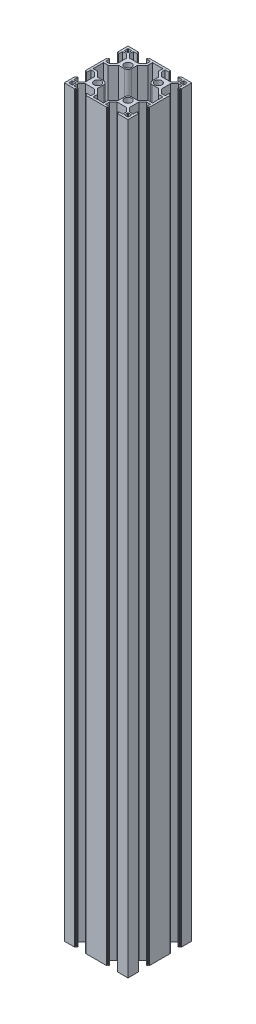
SolidWorks part; units mm, degrees
ref_plane "Front Plane" through (0, 0, 0) normal (0, 0, 1) x (1, 0, 0)
ref_plane "Top Plane" through (0, 0, 0) normal (0, 1, 0) x (1, 0, 0)
ref_plane "Right Plane" through (0, 0, 0) normal (1, 0, 0) x (0, 0, -1)
sketch "Sketch1" plane through (0, 0, 0) normal (0, 1, 0) x (1, 0, 0)
  line L0 (0, 30) -> (0, -30) construction
  line L1 (-30, -30) -> (30, -30)
  line L2 (-30, -30) -> (-30, 30)
  line L3 (-30, 30) -> (30, 30)
  line L4 (30, -30) -> (30, 30)
  line L5 (-30, -30) -> (30, 30) construction
  line L6 (-30, 30) -> (30, -30) construction
  line L7 (-30, 0) -> (30, 0) construction
  line L8 (-23.05, -28) -> (-6.95, -28)
  line L9 (-6.95, -28) -> (-6.95, -24.4)
  line L10 (-6.95, -24.4) -> (-10.615, -20.8)
  line L11 (-10.615, -20.8) -> (-19.385, -20.8)
  line L12 (-19.385, -20.8) -> (-23.05, -24.4)
  line L13 (-23.05, -24.4) -> (-23.05, -28)
  line L14 (10.615, -20.8) -> (19.385, -20.8)
  line L15 (6.95, -24.4) -> (10.615, -20.8)
  line L16 (6.95, -28) -> (6.95, -24.4)
  line L17 (23.05, -28) -> (6.95, -28)
  line L18 (23.05, -24.4) -> (23.05, -28)
  line L19 (19.385, -20.8) -> (23.05, -24.4)
  line L20 (19.385, 20.8) -> (23.05, 24.4)
  line L21 (23.05, 24.4) -> (23.05, 28)
  line L22 (23.05, 28) -> (6.95, 28)
  line L23 (6.95, 28) -> (6.95, 24.4)
  line L24 (6.95, 24.4) -> (10.615, 20.8)
  line L25 (10.615, 20.8) -> (19.385, 20.8)
  line L26 (-23.05, 24.4) -> (-23.05, 28)
  line L27 (-19.385, 20.8) -> (-23.05, 24.4)
  line L28 (-10.615, 20.8) -> (-19.385, 20.8)
  line L29 (-6.95, 24.4) -> (-10.615, 20.8)
  line L30 (-6.95, 28) -> (-6.95, 24.4)
  line L31 (-23.05, 28) -> (-6.95, 28)
  line L32 (-20.8, 19.385) -> (-24.4, 23.05)
  line L33 (-24.4, 23.05) -> (-28, 23.05)
  line L34 (-28, 23.05) -> (-28, 6.95)
  line L35 (-28, 6.95) -> (-24.4, 6.95)
  line L36 (-24.4, 6.95) -> (-20.8, 10.615)
  line L37 (-20.8, 10.615) -> (-20.8, 19.385)
  line L38 (-24.4, -23.05) -> (-28, -23.05)
  line L39 (-20.8, -19.385) -> (-24.4, -23.05)
  line L40 (-20.8, -10.615) -> (-20.8, -19.385)
  line L41 (-24.4, -6.95) -> (-20.8, -10.615)
  line L42 (-28, -6.95) -> (-24.4, -6.95)
  line L43 (-28, -23.05) -> (-28, -6.95)
  line L44 (20.8, -19.385) -> (24.4, -23.05)
  line L45 (24.4, -23.05) -> (28, -23.05)
  line L46 (28, -23.05) -> (28, -6.95)
  line L47 (28, -6.95) -> (24.4, -6.95)
  line L48 (24.4, -6.95) -> (20.8, -10.615)
  line L49 (20.8, -10.615) -> (20.8, -19.385)
  line L50 (24.4, 23.05) -> (28, 23.05)
  line L51 (20.8, 19.385) -> (24.4, 23.05)
  line L52 (20.8, 10.615) -> (20.8, 19.385)
  line L53 (24.4, 6.95) -> (20.8, 10.615)
  line L54 (28, 6.95) -> (24.4, 6.95)
  line L55 (28, 23.05) -> (28, 6.95)
  point P0 (0, 0)
  dimension "D1" = 60
  dimension "D2" = 16.1
  dimension "D3" = 8.77
  dimension "D4" = 3.6
  dimension "D5" = 7.2
  dimension "D6" = 2
  dimension "D7" = 6.95
extrude "Boss-Extrude1" add sketch "Sketch1" along normal blind 700
sketch "Sketch2" plane through (0, 700, 0) normal (0, 1, 0) x (1, 0, 0)
  line L0 (-19.1, -28) -> (-19.1, -29)
  line L1 (-23.05, -28) -> (-6.95, -28) construction
  line L2 (-30, -30) -> (30, -30) construction
  line L3 (-10.9, -28) -> (-10.9, -29)
  line L4 (-10.9, -29) -> (-9.9, -29)
  line L5 (-9.9, -29) -> (-9.9, -30)
  line L6 (-19.1, -29) -> (-20.1, -29)
  line L7 (-20.1, -29) -> (-20.1, -30)
  line L8 (-19.1, -28) -> (-10.9, -28)
  line L9 (-20.1, -30) -> (-9.9, -30)
  dimension "D1" = 8.2
  dimension "D2" = 3.95
  dimension "D3" = 1
  dimension "D4" = 1
extrude "Cut-Extrude1" cut sketch "Sketch2" against normal through all
mirror "Mirror1" about plane through (0, 0, 0) normal (1, 0, 0) of "Cut-Extrude1"
ref_axis "Axis1" through (0, 1050, 0) along (0, -1, 0)
pattern_circular "CirPattern1" count 4 over 360 about axis through (0, 1050, 0) along (0, -1, 0) of "Cut-Extrude1", "Mirror1"
sketch "Sketch4" plane through (0, 700, 0) normal (0, 1, 0) x (1, 0, 0)
  line L0 (19.385, 18.8) -> (9.797, 18.8) construction
  line L1 (-18.8, 18.8) -> (-18.8, 9.797)
  line L2 (18.8, -19.385) -> (18.8, -9.797) construction
  line L3 (28, 4.95) -> (28, -4.95)
  line L4 (-18.8, -9.797) -> (-18.8, -19.385) construction
  line L5 (4.95, -28) -> (-4.95, -28)
  line L6 (-9.797, 18.8) -> (-9.797, 13.197)
  line L7 (-28, -4.95) -> (-28, 4.95)
  line L8 (-18.8, 9.797) -> (-23.5611, 4.95)
  line L9 (-23.5611, 4.95) -> (-28, 4.95)
  line L10 (18.8, 18.8) -> (9.797, 18.8)
  line L11 (9.797, 18.8) -> (4.95, 23.5611)
  line L12 (4.95, 23.5611) -> (4.95, 28)
  line L13 (4.95, 28) -> (4.95, 28)
  line L14 (4.95, 28) -> (4.95, 28)
  line L15 (4.95, 28) -> (4.95, 28)
  line L16 (4.95, 28) -> (4.95, 28)
  line L17 (4.95, 28) -> (-4.95, 28)
  line L18 (-4.95, 28) -> (-4.95, 28)
  line L19 (-4.95, 28) -> (-4.95, 28)
  line L20 (-4.95, 28) -> (-4.95, 28)
  line L21 (-4.95, 28) -> (-4.95, 28)
  line L22 (-4.95, 28) -> (-4.95, 23.5611)
  line L23 (-4.95, 23.5611) -> (-9.797, 18.8)
  line L24 (-9.797, 18.8) -> (-18.8, 18.8)
  line L25 (28, 4.95) -> (23.5611, 4.95)
  line L26 (23.5611, 4.95) -> (18.8, 9.797)
  line L27 (18.8, 9.797) -> (18.8, 18.8)
  line L28 (18.8, -18.8) -> (18.8, -9.797)
  line L29 (18.8, -9.797) -> (23.5611, -4.95)
  line L30 (23.5611, -4.95) -> (28, -4.95)
  line L31 (4.95, -28) -> (4.95, -23.5611)
  line L32 (4.95, -23.5611) -> (9.797, -18.8)
  line L33 (9.797, -18.8) -> (18.8, -18.8)
  line L34 (-18.8, -18.8) -> (-9.797, -18.8)
  line L35 (-9.797, -18.8) -> (-4.95, -23.5611)
  line L36 (-4.95, -23.5611) -> (-4.95, -28)
  line L37 (-28, -4.95) -> (-23.5611, -4.95)
  line L38 (-23.5611, -4.95) -> (-18.8, -9.797)
  line L39 (-18.8, -9.797) -> (-18.8, -18.8)
  line L40 (-9.797, 18.8) -> (-19.385, 18.8) construction
  line L41 (-18.8, 19.385) -> (-18.8, 9.797) construction
  line L42 (18.8, 9.797) -> (18.8, 19.385) construction
  line L43 (9.797, -18.8) -> (19.385, -18.8) construction
  line L44 (-19.385, -18.8) -> (-9.797, -18.8) construction
  line L45 (-13.197, 9.797) -> (-18.8, 9.797)
  line L46 (9.797, 18.8) -> (9.797, 13.197)
  line L47 (13.197, 9.797) -> (18.8, 9.797)
  line L48 (-18.8, -9.797) -> (-13.197, -9.797)
  line L49 (-9.797, -13.197) -> (-9.797, -18.8)
  line L50 (9.797, -18.8) -> (9.797, -13.197)
  line L51 (13.197, -9.797) -> (18.8, -9.797)
  line L52 (-27.5, -28) -> (-24.9, -28)
  line L53 (24.9, -28) -> (27.5, -28)
  line L54 (24.4, -27.5) -> (24.4, -24.9)
  line L55 (24.9, -24.4) -> (27.5, -24.4)
  line L56 (28, -27.5) -> (28, -24.9)
  line L57 (24.4, -28) -> (28, -24.4) construction
  line L58 (24.4, -24.4) -> (28, -28) construction
  line L59 (-28, -24.9) -> (-28, -27.5)
  line L60 (-27.5, -24.4) -> (-24.9, -24.4)
  line L61 (-24.4, -24.9) -> (-24.4, -27.5)
  line L62 (-28, 27.5) -> (-28, 24.9)
  line L63 (-24.9, 28) -> (-27.5, 28)
  line L64 (-24.4, 27.5) -> (-24.4, 24.9)
  line L65 (-24.9, 24.4) -> (-27.5, 24.4)
  line L66 (27.5, 28) -> (24.9, 28)
  line L67 (28, 24.9) -> (28, 27.5)
  line L68 (27.5, 24.4) -> (24.9, 24.4)
  line L69 (24.4, 24.9) -> (24.4, 27.5)
  line L116 (28, 19.1) -> (29, 19.1)
  line L117 (29, 19.1) -> (29, 20.1)
  line L118 (29, 20.1) -> (30, 20.1)
  line L119 (30, 20.1) -> (30, 30)
  line L120 (30, 30) -> (20.1, 30)
  line L121 (20.1, 30) -> (20.1, 29)
  line L122 (20.1, 29) -> (19.1, 29)
  line L123 (19.1, 29) -> (19.1, 28)
  line L124 (19.1, 28) -> (23.05, 28)
  line L125 (23.05, 28) -> (23.05, 24.4)
  line L126 (23.05, 24.4) -> (19.385, 20.8)
  line L127 (19.385, 20.8) -> (10.615, 20.8)
  line L128 (10.615, 20.8) -> (6.95, 24.4)
  line L129 (6.95, 24.4) -> (6.95, 28)
  line L130 (6.95, 28) -> (10.9, 28)
  line L131 (10.9, 28) -> (10.9, 29)
  line L132 (10.9, 29) -> (9.9, 29)
  line L133 (9.9, 29) -> (9.9, 30)
  line L134 (9.9, 30) -> (-9.9, 30)
  line L135 (-9.9, 30) -> (-9.9, 29)
  line L136 (-9.9, 29) -> (-10.9, 29)
  line L137 (-10.9, 29) -> (-10.9, 28)
  line L138 (-10.9, 28) -> (-6.95, 28)
  line L139 (-6.95, 28) -> (-6.95, 24.4)
  line L140 (-6.95, 24.4) -> (-10.615, 20.8)
  line L141 (-10.615, 20.8) -> (-19.385, 20.8)
  line L142 (-19.385, 20.8) -> (-23.05, 24.4)
  line L143 (-23.05, 24.4) -> (-23.05, 28)
  line L144 (-23.05, 28) -> (-19.1, 28)
  line L145 (-19.1, 28) -> (-19.1, 29)
  line L146 (-19.1, 29) -> (-20.1, 29)
  line L147 (-20.1, 29) -> (-20.1, 30)
  line L148 (-20.1, 30) -> (-30, 30)
  line L149 (-30, 30) -> (-30, 20.1)
  line L150 (-30, 20.1) -> (-29, 20.1)
  line L151 (-29, 20.1) -> (-29, 19.1)
  line L152 (-29, 19.1) -> (-28, 19.1)
  line L153 (-28, 19.1) -> (-28, 23.05)
  line L154 (-28, 23.05) -> (-24.4, 23.05)
  line L155 (-24.4, 23.05) -> (-20.8, 19.385)
  line L156 (-20.8, 19.385) -> (-20.8, 10.615)
  line L157 (-20.8, 10.615) -> (-24.4, 6.95)
  line L158 (-24.4, 6.95) -> (-28, 6.95)
  line L159 (-28, 6.95) -> (-28, 10.9)
  line L160 (-28, 10.9) -> (-29, 10.9)
  line L161 (-29, 10.9) -> (-29, 9.9)
  line L162 (-29, 9.9) -> (-30, 9.9)
  line L163 (-30, 9.9) -> (-30, -9.9)
  line L164 (-30, -9.9) -> (-29, -9.9)
  line L165 (-29, -9.9) -> (-29, -10.9)
  line L166 (-29, -10.9) -> (-28, -10.9)
  line L167 (-28, -10.9) -> (-28, -6.95)
  line L168 (-28, -6.95) -> (-24.4, -6.95)
  line L169 (-24.4, -6.95) -> (-20.8, -10.615)
  line L170 (-20.8, -10.615) -> (-20.8, -19.385)
  line L171 (-20.8, -19.385) -> (-24.4, -23.05)
  line L172 (-24.4, -23.05) -> (-28, -23.05)
  line L173 (-28, -23.05) -> (-28, -19.1)
  line L174 (-28, -19.1) -> (-29, -19.1)
  line L175 (-29, -19.1) -> (-29, -20.1)
  line L176 (-29, -20.1) -> (-30, -20.1)
  line L177 (-30, -20.1) -> (-30, -30)
  line L178 (-30, -30) -> (-20.1, -30)
  line L179 (-20.1, -30) -> (-20.1, -29)
  line L180 (-20.1, -29) -> (-19.1, -29)
  line L181 (-19.1, -29) -> (-19.1, -28)
  line L182 (-19.1, -28) -> (-23.05, -28)
  line L183 (-23.05, -28) -> (-23.05, -24.4)
  line L184 (-23.05, -24.4) -> (-19.385, -20.8)
  line L185 (-19.385, -20.8) -> (-10.615, -20.8)
  line L186 (-10.615, -20.8) -> (-6.95, -24.4)
  line L187 (-6.95, -24.4) -> (-6.95, -28)
  line L188 (-6.95, -28) -> (-10.9, -28)
  line L189 (-10.9, -28) -> (-10.9, -29)
  line L190 (-10.9, -29) -> (-9.9, -29)
  line L191 (-9.9, -29) -> (-9.9, -30)
  line L192 (-9.9, -30) -> (9.9, -30)
  line L193 (9.9, -30) -> (9.9, -29)
  line L194 (9.9, -29) -> (10.9, -29)
  line L195 (10.9, -29) -> (10.9, -28)
  line L196 (10.9, -28) -> (6.95, -28)
  line L197 (6.95, -28) -> (6.95, -24.4)
  line L198 (6.95, -24.4) -> (10.615, -20.8)
  line L199 (10.615, -20.8) -> (19.385, -20.8)
  line L200 (19.385, -20.8) -> (23.05, -24.4)
  line L201 (23.05, -24.4) -> (23.05, -28)
  line L202 (23.05, -28) -> (19.1, -28)
  line L203 (19.1, -28) -> (19.1, -29)
  line L204 (19.1, -29) -> (20.1, -29)
  line L205 (20.1, -29) -> (20.1, -30)
  line L206 (20.1, -30) -> (30, -30)
  line L207 (30, -30) -> (30, -20.1)
  line L208 (30, -20.1) -> (29, -20.1)
  line L209 (29, -20.1) -> (29, -19.1)
  line L210 (29, -19.1) -> (28, -19.1)
  line L211 (28, -19.1) -> (28, -23.05)
  line L212 (28, -23.05) -> (24.4, -23.05)
  line L213 (24.4, -23.05) -> (20.8, -19.385)
  line L214 (20.8, -19.385) -> (20.8, -10.615)
  line L215 (20.8, -10.615) -> (24.4, -6.95)
  line L216 (24.4, -6.95) -> (28, -6.95)
  line L217 (28, -6.95) -> (28, -10.9)
  line L218 (28, -10.9) -> (29, -10.9)
  line L219 (29, -10.9) -> (29, -9.9)
  line L220 (29, -9.9) -> (30, -9.9)
  line L221 (30, -9.9) -> (30, 9.9)
  line L222 (30, 9.9) -> (29, 9.9)
  line L223 (29, 9.9) -> (29, 10.9)
  line L224 (29, 10.9) -> (28, 10.9)
  line L225 (28, 10.9) -> (28, 6.95)
  line L226 (28, 6.95) -> (24.4, 6.95)
  line L227 (24.4, 6.95) -> (20.8, 10.615)
  line L228 (20.8, 10.615) -> (20.8, 19.385)
  line L229 (20.8, 19.385) -> (24.4, 23.05)
  line L230 (24.4, 23.05) -> (28, 23.05)
  line L231 (28, 23.05) -> (28, 19.1)
  line L232 (28, 19.1) -> (29, 19.1)
  line L233 (29, 19.1) -> (29, 20.1)
  line L234 (29, 20.1) -> (30, 20.1)
  line L235 (30, 20.1) -> (30, 30)
  line L236 (30, 30) -> (20.1, 30)
  line L237 (20.1, 30) -> (20.1, 29)
  line L238 (20.1, 29) -> (19.1, 29)
  line L239 (19.1, 29) -> (19.1, 28)
  line L240 (19.1, 28) -> (23.05, 28)
  line L241 (23.05, 28) -> (23.05, 24.4)
  line L242 (23.05, 24.4) -> (19.385, 20.8)
  line L243 (19.385, 20.8) -> (10.615, 20.8)
  line L244 (10.615, 20.8) -> (6.95, 24.4)
  line L245 (6.95, 24.4) -> (6.95, 28)
  line L246 (6.95, 28) -> (10.9, 28)
  line L247 (10.9, 28) -> (10.9, 29)
  line L248 (10.9, 29) -> (9.9, 29)
  line L249 (9.9, 29) -> (9.9, 30)
  line L250 (9.9, 30) -> (-9.9, 30)
  line L251 (-9.9, 30) -> (-9.9, 29)
  line L252 (-9.9, 29) -> (-10.9, 29)
  line L253 (-10.9, 29) -> (-10.9, 28)
  line L254 (-10.9, 28) -> (-6.95, 28)
  line L255 (-6.95, 28) -> (-6.95, 24.4)
  line L256 (-6.95, 24.4) -> (-10.615, 20.8)
  line L257 (-10.615, 20.8) -> (-19.385, 20.8)
  line L258 (-19.385, 20.8) -> (-23.05, 24.4)
  line L259 (-23.05, 24.4) -> (-23.05, 28)
  line L260 (-23.05, 28) -> (-19.1, 28)
  line L261 (-19.1, 28) -> (-19.1, 29)
  line L262 (-19.1, 29) -> (-20.1, 29)
  line L263 (-20.1, 29) -> (-20.1, 30)
  line L264 (-20.1, 30) -> (-30, 30)
  line L265 (-30, 30) -> (-30, 20.1)
  line L266 (-30, 20.1) -> (-29, 20.1)
  line L267 (-29, 20.1) -> (-29, 19.1)
  line L268 (-29, 19.1) -> (-28, 19.1)
  line L269 (-28, 19.1) -> (-28, 23.05)
  line L270 (-28, 23.05) -> (-24.4, 23.05)
  line L271 (-24.4, 23.05) -> (-20.8, 19.385)
  line L272 (-20.8, 19.385) -> (-20.8, 10.615)
  line L273 (-20.8, 10.615) -> (-24.4, 6.95)
  line L274 (-24.4, 6.95) -> (-28, 6.95)
  line L275 (-28, 6.95) -> (-28, 10.9)
  line L276 (-28, 10.9) -> (-29, 10.9)
  line L277 (-29, 10.9) -> (-29, 9.9)
  line L278 (-29, 9.9) -> (-30, 9.9)
  line L279 (-30, 9.9) -> (-30, -9.9)
  line L280 (-30, -9.9) -> (-29, -9.9)
  line L281 (-29, -9.9) -> (-29, -10.9)
  line L282 (-29, -10.9) -> (-28, -10.9)
  line L283 (-28, -10.9) -> (-28, -6.95)
  line L284 (-28, -6.95) -> (-24.4, -6.95)
  line L285 (-24.4, -6.95) -> (-20.8, -10.615)
  line L286 (-20.8, -10.615) -> (-20.8, -19.385)
  line L287 (-20.8, -19.385) -> (-24.4, -23.05)
  line L288 (-24.4, -23.05) -> (-28, -23.05)
  line L289 (-28, -23.05) -> (-28, -19.1)
  line L290 (-28, -19.1) -> (-29, -19.1)
  line L291 (-29, -19.1) -> (-29, -20.1)
  line L292 (-29, -20.1) -> (-30, -20.1)
  line L293 (-30, -20.1) -> (-30, -30)
  line L294 (-30, -30) -> (-20.1, -30)
  line L295 (-20.1, -30) -> (-20.1, -29)
  line L296 (-20.1, -29) -> (-19.1, -29)
  line L297 (-19.1, -29) -> (-19.1, -28)
  line L298 (-19.1, -28) -> (-23.05, -28)
  line L299 (-23.05, -28) -> (-23.05, -24.4)
  line L300 (-23.05, -24.4) -> (-19.385, -20.8)
  line L301 (-19.385, -20.8) -> (-10.615, -20.8)
  line L302 (-10.615, -20.8) -> (-6.95, -24.4)
  line L303 (-6.95, -24.4) -> (-6.95, -28)
  line L304 (-6.95, -28) -> (-10.9, -28)
  line L305 (-10.9, -28) -> (-10.9, -29)
  line L306 (-10.9, -29) -> (-9.9, -29)
  line L307 (-9.9, -29) -> (-9.9, -30)
  line L308 (-9.9, -30) -> (9.9, -30)
  line L309 (9.9, -30) -> (9.9, -29)
  line L310 (9.9, -29) -> (10.9, -29)
  line L311 (10.9, -29) -> (10.9, -28)
  line L312 (10.9, -28) -> (6.95, -28)
  line L313 (6.95, -28) -> (6.95, -24.4)
  line L314 (6.95, -24.4) -> (10.615, -20.8)
  line L315 (10.615, -20.8) -> (19.385, -20.8)
  line L316 (19.385, -20.8) -> (23.05, -24.4)
  line L317 (23.05, -24.4) -> (23.05, -28)
  line L318 (23.05, -28) -> (19.1, -28)
  line L319 (19.1, -28) -> (19.1, -29)
  line L320 (19.1, -29) -> (20.1, -29)
  line L321 (20.1, -29) -> (20.1, -30)
  line L322 (20.1, -30) -> (30, -30)
  line L323 (30, -30) -> (30, -20.1)
  line L324 (30, -20.1) -> (29, -20.1)
  line L325 (29, -20.1) -> (29, -19.1)
  line L326 (29, -19.1) -> (28, -19.1)
  line L327 (28, -19.1) -> (28, -23.05)
  line L328 (28, -23.05) -> (24.4, -23.05)
  line L329 (24.4, -23.05) -> (20.8, -19.385)
  line L330 (20.8, -19.385) -> (20.8, -10.615)
  line L331 (20.8, -10.615) -> (24.4, -6.95)
  line L332 (24.4, -6.95) -> (28, -6.95)
  line L333 (28, -6.95) -> (28, -10.9)
  line L334 (28, -10.9) -> (29, -10.9)
  line L335 (29, -10.9) -> (29, -9.9)
  line L336 (29, -9.9) -> (30, -9.9)
  line L337 (30, -9.9) -> (30, 9.9)
  line L338 (30, 9.9) -> (29, 9.9)
  line L339 (29, 9.9) -> (29, 10.9)
  line L340 (29, 10.9) -> (28, 10.9)
  line L341 (28, 10.9) -> (28, 6.95)
  line L342 (28, 6.95) -> (24.4, 6.95)
  line L343 (24.4, 6.95) -> (20.8, 10.615)
  line L344 (20.8, 10.615) -> (20.8, 19.385)
  line L345 (20.8, 19.385) -> (24.4, 23.05)
  line L346 (24.4, 23.05) -> (28, 23.05)
  line L347 (28, 23.05) -> (28, 19.1)
  circle A0 centre (14.2985, 14.2985) radius 3.4
  arc A1 (13.197, -9.797) -> (9.797, -13.197) centre (13.197, -13.197) ccw
  arc A2 (-9.797, -13.197) -> (-13.197, -9.797) centre (-13.197, -13.197) ccw
  arc A3 (13.197, 9.797) -> (9.797, 13.197) centre (13.197, 13.197) cw
  arc A4 (-9.797, 13.197) -> (-13.197, 9.797) centre (-13.197, 13.197) cw
  circle A5 centre (14.2985, -14.2985) radius 3.4
  circle A6 centre (-14.2985, -14.2985) radius 3.4
  circle A7 centre (-14.2985, 14.2985) radius 3.4
  arc A8 (24.4, -27.5) -> (24.9, -28) centre (24.9, -27.5) ccw
  arc A9 (28, -27.5) -> (27.5, -28) centre (27.5, -27.5) cw
  arc A10 (28, -24.9) -> (27.5, -24.4) centre (27.5, -24.9) ccw
  arc A11 (24.4, -24.9) -> (24.9, -24.4) centre (24.9, -24.9) cw
  arc A12 (-27.5, -28) -> (-28, -27.5) centre (-27.5, -27.5) cw
  arc A13 (-27.5, -24.4) -> (-28, -24.9) centre (-27.5, -24.9) ccw
  arc A14 (-24.9, -24.4) -> (-24.4, -24.9) centre (-24.9, -24.9) cw
  arc A15 (-24.9, -28) -> (-24.4, -27.5) centre (-24.9, -27.5) ccw
  arc A16 (-28, 27.5) -> (-27.5, 28) centre (-27.5, 27.5) cw
  arc A17 (-24.4, 27.5) -> (-24.9, 28) centre (-24.9, 27.5) ccw
  arc A18 (-24.4, 24.9) -> (-24.9, 24.4) centre (-24.9, 24.9) cw
  arc A19 (-28, 24.9) -> (-27.5, 24.4) centre (-27.5, 24.9) ccw
  arc A20 (27.5, 28) -> (28, 27.5) centre (27.5, 27.5) cw
  arc A21 (27.5, 24.4) -> (28, 24.9) centre (27.5, 24.9) ccw
  arc A22 (24.9, 24.4) -> (24.4, 24.9) centre (24.9, 24.9) cw
  arc A23 (24.9, 28) -> (24.4, 27.5) centre (24.9, 27.5) ccw
  point P102 (26.2, -26.2)
  point P104 (14.2985, 18.8)
  point P106 (18.8, 14.2985)
  point P140 (0, 0)
  point P239 (0, 0)
  dimension "D3" = 6.8
  dimension "D4" = 3.4
  dimension "D6" = 0.5
  dimension "D1" = 0
  dimension "D2" = 2
  dimension "D5" = 4
  dimension "D7" = 4
extrude "Cut-Extrude2" cut sketch "Sketch4" against normal through all contours L6 A4 L45 L8 L9 L7 L37 L38 L48 A2 L49 L35 L36 L5 L31 L32 L50 A1 L51 L29 L30 L3 L25 L26 L47 A3 L46 L11 L12 L17 L22 L23 | A7 | A0 | L66 A23 L69 A22 L68 A21 L67 A20 | L62 A19 L65 A18 L64 A17 L63 A16 | L52 A15 L61 A14 L60 A13 L59 A12 | A11 L54 A8 L53 A9 L56 A10 L55 | A6 | A5 region at (0, 700, 0) region at (-26.2, 700, 26.2) region at (26.2, 700, 26.2) region at (-26.2, 700, -26.2) region at (26.2, 700, -26.2) region at (14.2985, 700, -14.2985) region at (-14.2985, 700, -14.2985)
fillet "Fillet1" radius 0.2 16 edges at (28, 350, -19.1) (30, 350, -20.1) (29, 350, -20.1) (29, 350, -19.1) (28, 350, 10.9) (29, 350, 9.9) (28, 350, 19.1) (29, 350, 20.1) (30, 350, 20.1) (29, 350, 19.1) (29, 350, 10.9) (30, 350, 9.9) (30, 350, -9.9) (29, 350, -9.9) (29, 350, -10.9) (28, 350, -10.9)
fillet "Fillet2" radius 0.2 20 edges at (-20.1, 0, -29.5) (-20.1, 700, -29.5) (-20.1, 350, -29) (-19.6, 0, -29) (-19.1, 350, -29) (-19.6, 700, -29) (-9.9, 350, -30) (-10.9, 350, -28) (-10.9, 350, -29) (-9.9, 350, -29) (19.1, 350, -28) (19.1, 350, -29) (20.1, 350, -29) (20.1, 350, -30) (10.9, 350, -28) (10.9, 350, -29) (9.9, 350, -29) (9.9, 350, -30) (-19.1, 350, -28) (-20.1, 350, -30)
fillet "Fillet3" radius 0.2 14 edges at (-29, 350, 9.9) (-29, 350, -20.1) (-30, 350, -20.1) (-29, 350, -19.1) (-28, 350, -10.9) (-29, 350, -10.9) (-29, 350, -9.9) (-30, 350, -9.9) (-29, 350, 10.9) (-30, 350, 9.9) (-28, 350, 19.1) (-29, 350, 19.1) (-29, 350, 20.1) (-30, 350, 20.1)
fillet "Fillet4" radius 0.2 16 edges at (-19.1, 350, 28) (10.9, 350, 28) (19.1, 350, 28) (20.1, 350, 29) (-10.9, 350, 28) (-9.9, 350, 29) (9.9, 350, 29) (-20.1, 350, 29) (19.1, 350, 29) (20.1, 350, 30) (10.9, 350, 29) (9.9, 350, 30) (-9.9, 350, 30) (-10.9, 350, 29) (-19.1, 350, 29) (-20.1, 350, 30)
